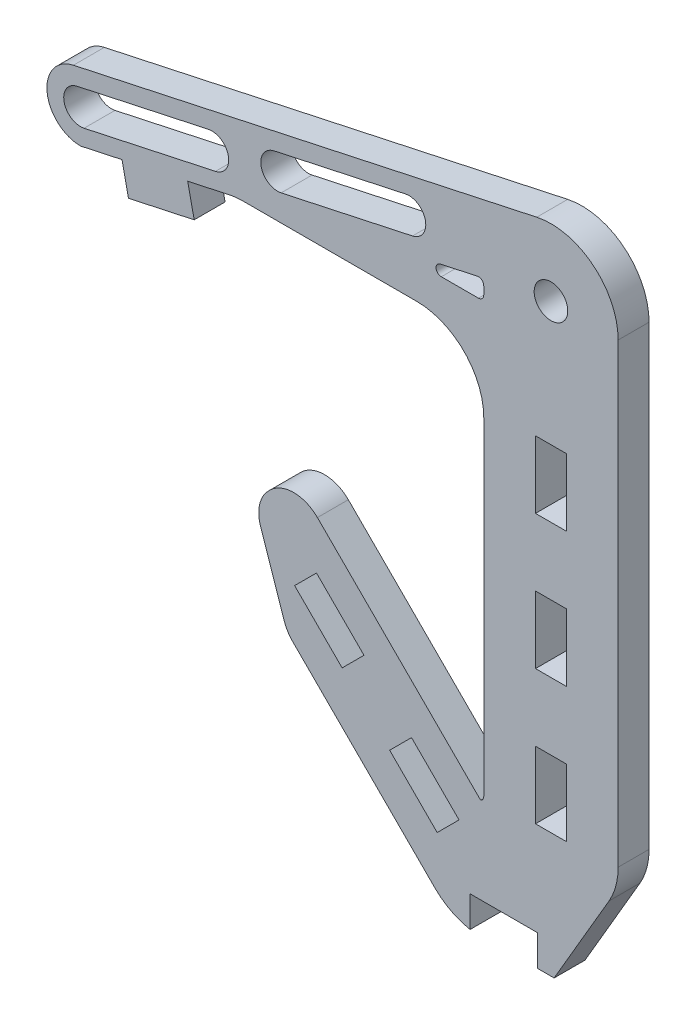
SolidWorks part; units mm, degrees
ref_plane "Front Plane" through (0, 0, 0) normal (0, 0, 1) x (1, 0, 0)
ref_plane "Top Plane" through (0, 0, 0) normal (0, 1, 0) x (1, 0, 0)
ref_plane "Right Plane" through (0, 0, 0) normal (1, 0, 0) x (0, 0, -1)
sketch "Sketch1" plane through (0, 0, 0) normal (0, 0, 1) x (1, 0, 0)
  line L0 (217.7702, 9.1265) -> (220.9452, 9.1265)
  line L1 (223.5229, 116.9897) -> (223.5229, 113.2357)
  line L2 (223.5229, 30.6857) -> (222.9299, 31.2787)
  line L3 (236.8202, 9.1265) -> (248.9229, 29.8834)
  line L4 (190.8294, 36.0673) -> (217.7702, 9.1265)
  line L5 (180.072, 59.0768) -> (187.6019, 66.6067)
  line L6 (183.471, 62.4758) -> (243.9272, 2.0196) construction
  line L7 (187.9611, 57.9856) -> (192.092, 62.1166)
  line L8 (200.8384, 45.1083) -> (204.9694, 49.2392)
  line L9 (187.9611, 57.9856) -> (200.8384, 45.1083)
  line L10 (209.8187, 36.128) -> (213.9496, 40.259)
  line L11 (218.799, 27.1478) -> (222.9299, 31.2787)
  line L12 (218.799, 27.1478) -> (209.8187, 36.128)
  line L13 (192.092, 62.1166) -> (187.6019, 66.6067)
  line L14 (213.9496, 40.259) -> (204.9694, 49.2392)
  line L15 (233.6452, 9.1265) -> (236.8202, 9.1265)
  line L16 (248.9229, 29.8834) -> (248.9229, 36.2334)
  line L17 (223.5229, 119.5857) -> (248.9229, 119.5857) construction
  line L18 (223.5229, 106.8857) -> (147.3229, 106.8857) construction
  line L19 (233.5424, 131.9996) -> (145.9826, 113.0926)
  line L20 (147.3229, 100.5357) -> (176.7303, 106.8857)
  line L21 (206.1377, 113.2357) -> (223.5229, 113.2357)
  line L22 (176.7303, 106.8857) -> (223.5229, 106.8857)
  line L23 (206.1377, 113.2357) -> (223.5229, 116.9897)
  line L24 (223.5229, 106.8857) -> (223.5229, 30.6857)
  line L25 (147.3229, 106.8857) -> (240.0259, 126.9032) construction
  line L26 (147.3229, 106.8857) -> (172.1507, 112.2468) construction
  line L27 (146.6528, 109.9891) -> (171.4805, 115.3502)
  line L28 (147.993, 103.7822) -> (172.8208, 109.1433)
  line L29 (184.5646, 114.9273) -> (209.3923, 120.2884) construction
  line L30 (183.8944, 118.0308) -> (208.7222, 123.3919)
  line L31 (185.2347, 111.8239) -> (210.0625, 117.185)
  line L32 (190.8294, 36.0673) -> (186.3393, 40.5574)
  line L33 (233.6452, 14.9685) -> (220.9452, 14.9685)
  line L34 (233.6452, 14.9685) -> (233.6452, 9.1265)
  line L35 (248.9229, 36.2334) -> (248.9229, 99.7334)
  line L36 (220.9452, 14.9685) -> (220.9452, 9.1265)
  line L37 (227.2952, 9.1265) -> (227.2952, 14.9685) construction
  line L38 (233.6452, 12.0475) -> (220.9452, 12.0475) construction
  line L39 (186.3393, 40.5574) -> (180.072, 59.0768)
  line L40 (236.2229, 119.5857) -> (236.2229, 9.1265) construction
  line L41 (233.3019, 32.6061) -> (233.3019, 45.3061)
  line L42 (233.3019, 58.0061) -> (239.1439, 58.0061)
  line L43 (233.3019, 58.0061) -> (233.3019, 70.7061)
  line L44 (233.3019, 70.7061) -> (239.1439, 70.7061)
  line L45 (239.1439, 58.0061) -> (239.1439, 70.7061)
  line L46 (233.3019, 58.0061) -> (239.1439, 70.7061) construction
  line L47 (233.3019, 70.7061) -> (239.1439, 58.0061) construction
  line L48 (233.3019, 45.3061) -> (239.1439, 45.3061)
  line L49 (239.1439, 32.6061) -> (239.1439, 45.3061)
  line L50 (233.3019, 32.6061) -> (239.1439, 32.6061)
  line L51 (233.3019, 83.4061) -> (233.3019, 96.1061)
  line L52 (248.9229, 99.7334) -> (248.9229, 119.5857)
  line L53 (233.3019, 96.1061) -> (239.1439, 96.1061)
  line L54 (239.1439, 83.4061) -> (239.1439, 96.1061)
  line L55 (233.3019, 83.4061) -> (239.1439, 83.4061)
  arc A0 (248.9229, 119.5857) -> (233.5424, 131.9996) centre (236.2229, 119.5857) ccw
  circle A1 centre (236.2229, 119.5857) radius 3.175
  arc A2 (145.9826, 113.0926) -> (147.3229, 100.5357) centre (147.3229, 106.8857) ccw
  arc A3 (146.6528, 109.9891) -> (147.993, 103.7822) centre (147.3229, 106.8857) ccw
  arc A4 (172.8208, 109.1433) -> (171.4805, 115.3502) centre (172.1507, 112.2468) ccw
  arc A5 (183.8944, 118.0308) -> (185.2347, 111.8239) centre (184.5646, 114.9273) ccw
  arc A6 (210.0625, 117.185) -> (208.7222, 123.3919) centre (209.3923, 120.2884) ccw
  point P31 (159.7368, 109.5662)
  point P38 (227.2952, 12.0475)
  point P39 (196.9785, 117.6079)
  point P49 (236.2229, 64.3561)
  dimension "D5" = 25.4
  dimension "D11" = 76.2
  dimension "D13" = 12.7
  dimension "D15" = 3.175
  dimension "D1" = 50.8
  dimension "D2" = 25.4
  dimension "D3" = 45
  dimension "D4" = 38.1
  dimension "D6" = 5.842
  dimension "D7" = 6.35
  dimension "D10" = 88.9
  dimension "D12" = 12.7
  dimension "D14" = 6.35
  dimension "D16" = 25.4
  dimension "D18" = 5.842
  dimension "D19" = 12.7
  dimension "D20" = 6.35
  dimension "D21" = 19.05
  dimension "D22" = 9.525
  dimension "D23" = 12.7
  dimension "D24" = 5.842
  dimension "D8" = 12.7
  dimension "D9" = 12.7
  dimension "D17" = 2
extrude "Boss-Extrude1" add sketch "Sketch1" along normal blind 5.842
fillet "Fillet3" radius 12.7 4 edges at (223.5229, 106.8857, 2.921) (176.7303, 106.8857, 2.921) (248.9229, 29.8834, 2.921) (217.7702, 9.1265, 2.921)
fillet "Fillet4" radius 1 3 edges at (223.5229, 113.2357, 2.921) (223.5229, 116.9897, 2.921) (206.1377, 113.2357, 2.921)
fillet "Fillet5" radius 1 1 edges at (223.5229, 30.6857, 2.921)
sketch "Sketch4" plane through (0, 0, 5.842) normal (0, 0, 1) x (1, 0, 0)
  line L0 (192.092, 62.1166) -> (222.5908, 31.6177)
  line L1 (222.5908, 31.6177) -> (222.9299, 31.2787)
  line L2 (222.9299, 31.2787) -> (218.799, 27.1478)
  line L3 (218.799, 27.1478) -> (187.9611, 57.9856)
  line L4 (200.8384, 45.1083) -> (187.9611, 57.9856) construction
  line L5 (187.9611, 57.9856) -> (192.092, 62.1166) construction
  line L6 (187.9611, 57.9856) -> (192.092, 62.1166)
extrude "Boss-Extrude2" add sketch "Sketch4" against normal up to surface (5.842 mm away) up to face at (236.2229, 38.9561, 0)
sketch "Sketch5" plane through (0, 0, 5.842) normal (0, 0, 1) x (1, 0, 0)
  line L0 (180.8667, 59.8715) -> (230.7534, 9.9848) construction
  line L1 (187.6019, 66.6067) -> (180.072, 59.0768) construction
  line L2 (222.9299, 31.2787) -> (187.6019, 66.6067) construction
  line L3 (191.9124, 52.9567) -> (187.7815, 48.8258)
  line L4 (200.8927, 43.9764) -> (196.7617, 39.8455)
  line L5 (196.7617, 39.8455) -> (187.7815, 48.8258)
  line L6 (200.8927, 43.9764) -> (191.9124, 52.9567)
  line L7 (209.8729, 34.9962) -> (205.742, 30.8653)
  line L8 (214.7223, 21.885) -> (205.742, 30.8653)
  line L9 (218.8532, 26.0159) -> (209.8729, 34.9962)
  line L10 (218.8532, 26.0159) -> (214.7223, 21.885)
  point P9 (189.8469, 50.8912)
  dimension "D1" = 5.842
  dimension "D3" = 12.7
  dimension "D5" = 9.525
  dimension "D2" = 12.7
  dimension "D4" = 2
extrude "Cut-Extrude1" cut sketch "Sketch5" against normal through all
fillet "Fillet6" radius 6.35 3 edges at (187.6019, 66.6067, 2.921) (186.3393, 40.5574, 2.921) (180.072, 59.0768, 2.921)
sketch "Sketch6" plane through (0, 0, 5.842) normal (0, 0, 1) x (1, 0, 0)
  line L0 (161.3641, 103.5676) -> (162.5972, 97.8572) construction
  line L1 (147.3229, 100.5357) -> (175.4053, 106.5996) construction
  line L2 (168.8041, 99.1975) -> (156.3902, 96.5169)
  line L3 (156.3902, 96.5169) -> (155.1572, 102.2273)
  line L4 (168.8041, 99.1975) -> (167.5711, 104.9079)
  line L5 (167.5711, 104.9079) -> (155.1572, 102.2273)
  point P7 (162.5972, 97.8572)
  dimension "D1" = 5.842
  dimension "D2" = 12.7
extrude "Boss-Extrude3" add sketch "Sketch6" against normal up to surface (5.842 mm away) up to face at (212.2976, 28.4406, 0)
